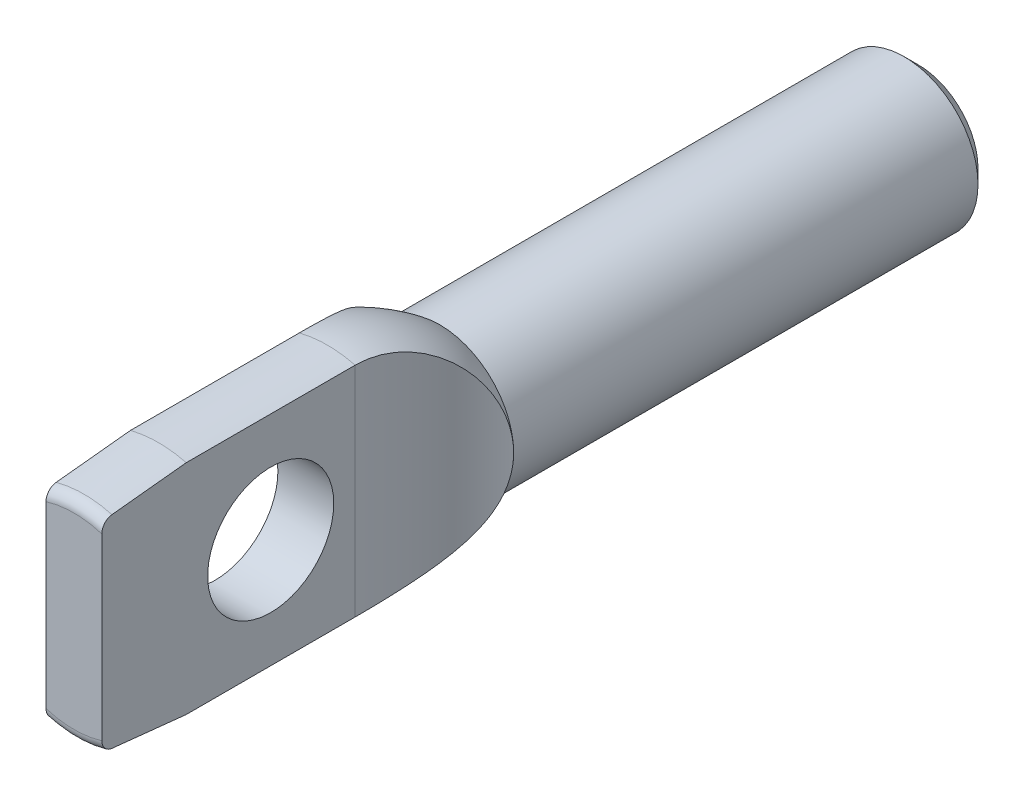
SolidWorks part; units mm, degrees
ref_plane "Front Plane" through (0, 0, 0) normal (0, 0, 1) x (1, 0, 0)
ref_plane "Top Plane" through (0, 0, 0) normal (0, 1, 0) x (1, 0, 0)
ref_plane "Right Plane" through (0, 0, 0) normal (1, 0, 0) x (0, 0, -1)
sketch "Sketch1" plane through (0, 0, 0) normal (1, 0, 0) x (0, 0, -1)
  line L0 (5.5562, 0) -> (7.1437, 0) construction
  line L1 (-4.7625, 3.175) -> (5.5562, 3.175)
  line L2 (-4.7625, 3.175) -> (-4.7625, -3.175)
  line L3 (-4.7625, -3.175) -> (5.5562, -3.175)
  line L4 (5.5562, 3.175) -> (5.5562, -3.175)
  line L5 (-4.7625, 3.175) -> (5.5562, -3.175) construction
  line L6 (-4.7625, -3.175) -> (5.5562, 3.175) construction
  line L7 (7.1437, 0) -> (19.05, 0) construction
  line L8 (19.05, 2.0828) -> (19.05, -2.0828) construction
  line L9 (19.0004, 2.1687) -> (19.7941, 2.1687) construction
  line L10 (19.7941, 2.1687) -> (19.3973, 1.4813) construction
  line L11 (19.3973, 1.4813) -> (19.3973, 1.5672) construction
  line L12 (19.0004, 2.1687) -> (19.3973, 1.4813) construction
  line L13 (19.05, 2.0828) -> (19.7445, 2.0828) construction
  line L14 (19.3477, 1.5672) -> (19.4469, 1.5672) construction
  line L15 (19.0252, 2.1258) -> (19.7693, 2.1258) construction
  line L16 (19.3973, 2.0828) -> (19.3973, 2.1687) construction
  line L17 (19.05, -2.0828) -> (17.0656, -2.0828) construction
  circle A0 centre (0, 0) radius 1.778
  point P3 (0.3969, 0)
  point P14 (19.05, 0)
  point P21 (19.3973, 2.0828)
  point P24 (19.3973, 1.5672)
  point P27 (19.3973, 2.1258)
  dimension "D1" = 60
  dimension "D2" = 0.0992
  dimension "D3" = 1.9844
sketch "Sketch2" plane through (0, 0, 0) normal (0, 0, 1) x (1, 0, 0)
  line L0 (-0.7874, 0) -> (0.7874, 0) construction
  point P3 (0, 0)
  dimension "Head Thickness (J)" = 1.5748
sketch "Sketch3" plane through (0, 0, 0) normal (1, 0, 0) x (0, 0, -1)
  line L0 (19.05, 0) -> (19.05, 1.6859)
  line L1 (18.6531, 2.0828) -> (5.5562, 2.0828)
  line L2 (5.5562, 3.175) -> (5.5562, -3.175) construction
  line L4 (2.3824, 3.175) -> (-2.3813, 3.175)
  line L5 (-4.7625, 2.6458) -> (-4.7625, 0)
  line L6 (-4.7625, 3.175) -> (-4.7625, -3.175) construction
  line L7 (-4.7625, 0) -> (19.05, 0)
  line L8 (19.05, 1.6859) -> (18.6531, 2.0828)
  line L9 (-4.7625, 2.6458) -> (-4.7625, 3.175) construction
  line L10 (-4.7625, 3.175) -> (-3.9688, 3.175) construction
  line L12 (-4.4771, 2.9617) -> (-2.3813, 3.175)
  line L13 (-3.9688, 3.175) -> (-3.175, 3.175) construction
  line L14 (-3.175, 3.175) -> (-2.3813, 3.175) construction
  arc A0 (5.5562, 2.0828) -> (2.3824, 3.175) centre (2.3824, -1.9827) ccw
  arc A1 (5.5562, 2.0828) -> (7.1437, 0) centre (2.3824, -1.9827) cw construction
  arc A3 (-4.7625, 2.6458) -> (-4.4771, 2.9617) centre (-4.445, 2.6458) cw
  point P1 (19.05, 2.0828)
  point P21 (-4.7625, 3.175)
  dimension "D3" = 0.3175
  dimension "D1" = 0.3969
  dimension "D2" = 45
  dimension "D4" = 0.5292
  dimension "D5" = 0.7937
revolve "Body Revolve" add sketch "Sketch3" angle 360 about L7
sketch "Sketch5" plane through (0, 0, 0) normal (0, 1, 0) x (1, 0, 0)
  line L0 (0, 0) -> (0, -4.7625) construction
  line L2 (-3.9624, 5.5562) -> (-3.9624, -4.7625)
  line L3 (-3.9624, -4.7625) -> (-0.7874, -4.7625)
  line L4 (-0.7874, -4.7625) -> (-0.7874, 2.3824)
  line L5 (-2.0828, 5.5562) -> (-3.9624, 5.5562)
  line L6 (-0.7874, 0) -> (0.7874, 0) construction
  line L8 (2.0828, 5.5562) -> (-2.0828, 5.5562) construction
  line L9 (2.0828, 5.5562) -> (3.9624, 5.5562)
  line L10 (0.7874, -4.7625) -> (0.7874, 2.3824)
  line L11 (3.9624, -4.7625) -> (0.7874, -4.7625)
  line L12 (3.9624, 5.5562) -> (3.9624, -4.7625)
  arc A0 (-0.7874, 2.3824) -> (-2.0828, 5.5562) centre (-5.3233, 2.3824) ccw
  arc A1 (0.7874, 2.3824) -> (2.0828, 5.5562) centre (5.3233, 2.3824) cw
  point P19 (-0.7874, 0)
  point P28 (0.7874, 0)
  dimension "D1" = 3.175
extrude "Head Cut" cut sketch "Sketch5" against normal through all both and the other way through all
sketch "Sketch6" plane through (0, 0, 0) normal (1, 0, 0) x (0, 0, -1)
  circle A1 centre (0, 0) radius 1.778
  circle A2 centre (0, 0) radius 1.778
  dimension "D1" = 0
extrude "Hole Cut" cut sketch "Sketch6" against normal through all both and the other way through all
ref_axis "Center Axis 1" through (0, 0, -31.4706) along (0, 0, 1)
ref_axis "Center Axis 2" through (-0.7874, 0, 0) along (1, 0, 0)
ref_plane "Contact Plane 1" through (0, 0, -19.05) normal (0, 0, -1) x (-1, 0, 0)
ref_plane "Contact Plane 2" through (0, 0, -7.1437) normal (0, 0, 1) x (1, 0, 0)
ref_plane "Split Plane" [suppressed] through (0, 0, -7.1437) normal (0, 0, 1) x (1, 0, 0)
split "Split1" [suppressed] bodies to split 106
sketch "Sketch7" [suppressed] plane through (0, 0, -19.05) normal (0, 0, -1) x (-1, 0, 0)
  circle A0 centre (0, 0) radius 2.0828 construction
  circle A1 centre (0, 0) radius 2.0828
curve "Helix/Spiral1" [suppressed] pitch 0.7937 height 12.7 turns 16
sketch "Sketch8" [suppressed] plane through (0, 0, 0) normal (1, 0, 0) x (0, 0, -1)
  line L0 (19.0252, 2.1258) -> (19.7693, 2.1258)
  line L1 (19.7693, 2.1258) -> (19.4469, 1.5672)
  line L2 (19.4469, 1.5672) -> (19.3477, 1.5672)
  line L3 (19.3477, 1.5672) -> (19.0252, 2.1258)
sweep "Thread Cut Sweep" [suppressed] cut profiles "Sketch8" path "Helix/Spiral1"
sketch "Sketch9" [suppressed] plane through (0, 0, -7.1437) normal (0, 0, 1) x (1, 0, 0)
  circle A1 centre (0, 0) radius 2.0828
  circle A2 centre (0, 0) radius 2.0828
  dimension "D1" = 0
extrude "Thread Extrude" [suppressed] add sketch "Sketch9" against normal through all draft 40
equation "\"D2@Sketch1\"=\"Pitch@Sketch1\"/8"
equation "\"D1@Sketch3\"=\"Pitch@Sketch1\" / 2"
equation "\"D1@Sketch5\"=\"Head Width (H)@Sketch1\"/2"
equation "\"D3@Helix/Spiral1\"=\"Thread Length (B)@Sketch1\"+\"Pitch@Sketch1\""
equation "\"D4@Helix/Spiral1\"=\"Pitch@Sketch1\""
equation "\"D4@Sketch3\"=\"Pitch@Sketch1\" / 1.5"
equation "\"D5@Sketch3\"=\"pitch@sketch1\""
equation "\"D3@Sketch1\"=\"Pitch@Sketch1\"*2.5"
